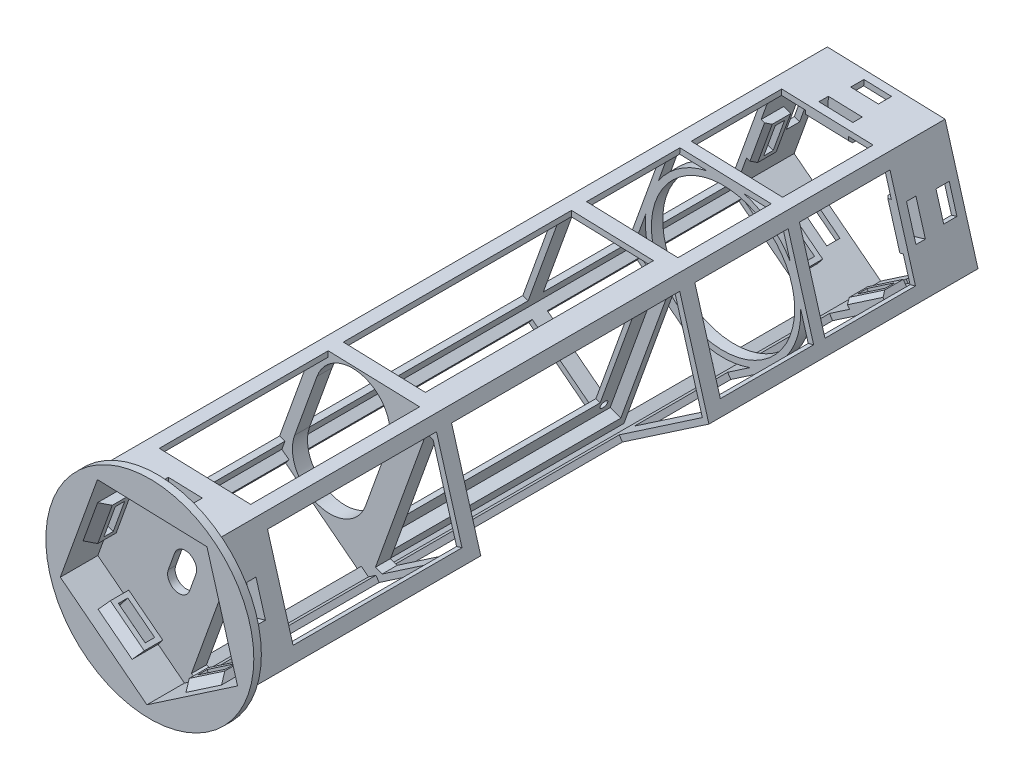
SolidWorks part; units mm, degrees
note: '?' marks a value the reader was unsure of.
ref_plane "Front Plane" through (0, 0, 0) normal (0, 0, 1) x (1, 0, 0)
ref_plane "Top Plane" through (0, 0, 0) normal (0, 1, 0) x (1, 0, 0)
ref_plane "Right Plane" through (0, 0, 0) normal (1, 0, 0) x (0, 0, -1)
sketch "Sketch3" plane through (0, 0, 0) normal (0, 0, 1) x (1, 0, 0)
  line L0 (0, 0) -> (16.2851, 21.0012) construction
  line L1 (15.1489, 19.536) -> (-13.8986, 20.4445)
  line L2 (-13.8986, 20.4445) -> (-23.7387, -6.9006)
  line L3 (-23.7387, -6.9006) -> (-0.7728, -24.7093)
  line L4 (-0.7728, -24.7093) -> (23.2611, -8.3705)
  line L5 (0, 0) -> (29.9163, 0) construction
  line L6 (0, 0) -> (25.0057, -8.9983) construction
  line L10 (-0.8307, -26.5625) -> (25.0057, -8.9983)
  line L11 (25.0057, -8.9983) -> (16.2851, 21.0012)
  line L12 (16.2851, 21.0012) -> (-14.941, 21.9778)
  line L13 (-14.941, 21.9778) -> (-25.5191, -7.4182)
  line L14 (-25.5191, -7.4182) -> (-0.8307, -26.5625)
  line L15 (23.2611, -8.3705) -> (15.1489, 19.536)
  circle A0 centre (0, 0) radius 20 construction
  dimension "D2" = 40
extrude "Boss-Extrude2" add sketch "Sketch3" along normal blind 190
ref_plane "Plane1" through (0, 0, 95) normal (0, 0, 1) x (1, 0, 0)
sketch "Sketch4" plane through (-20.23, 7.2798, 21.5) normal (0.9409, -0.3386, 0) x (-0.1146, -0.3186, -0.9409)
  line L8 (-154.443, -68.4581) -> (24.334, -4.1249)
  line L9 (-144.0928, -64.7335) -> (13.9838, -7.8495)
  line L11 (-162.6511, -45.6486) -> (16.126, 18.6845)
  line L12 (-152.3008, -41.9241) -> (5.7758, 14.96)
  line L14 (4.5907, 18.2532) -> (15.1689, -11.1427)
  line L15 (5.7758, 14.96) -> (13.9838, -7.8495)
  line L17 (-153.4859, -38.6308) -> (-142.9077, -68.0268)
  line L18 (-152.3008, -41.9241) -> (-144.0928, -64.7335)
  dimension "D1" = 3.5
  dimension "D2" = 3.5
  dimension "D3" = 11
  dimension "D4" = 11
extrude "Cut-Extrude1" cut sketch "Sketch4" along normal up to next
ref_point "Point1"
ref_axis "Axis1" through (0, 0, 190) along (0, 0, 1)?
pattern_circular "CirPattern1" count 5 over 360 about axis through (0, 0, 0) along (0, 0, 1) of "Cut-Extrude1"
ref_plane "Plane2" through (0, 0, 95) normal (0, 0, 1) x (1, 0, 0)
sketch "Sketch5" plane through (0, 0, 95) normal (0, 0, 1) x (1, 0, 0)
  line L0 (-2.0696, -25.6018) -> (14.7182, 21.0502) construction
  line L2 (-24.1133, -8.5083) -> (-1.8275, -25.7895) construction
  line L3 (23.2611, -8.3705) -> (0, 0) construction
  line L4 (-5.5594, -22.8957) -> (10.3043, 21.1882)
  line L8 (-2.0696, -25.6018) -> (-5.5594, -22.8957)
  line L10 (14.7182, 21.0502) -> (10.3043, 21.1882)
  line L11 (-2.0696, -25.6018) -> (14.7182, 21.0502)
  line L12 (-22.8004, 22.2236) -> (6.2471, 21.3151) construction
  dimension "D1" = 18
  dimension "D2" = 4.2
extrude "Boss-Extrude3" add sketch "Sketch5" along normal mid plane 64.5
sketch "Sketch6" plane through (0, 0, 127.25) normal (0, 0, 1) x (1, 0, 0)
  line L5 (-25.5191, -7.4182) -> (-0.8307, -26.5625)
  line L6 (-0.8307, -26.5625) -> (25.0057, -8.9983)
  line L7 (25.0057, -8.9983) -> (16.2851, 21.0012)
  line L8 (16.2851, 21.0012) -> (-14.941, 21.9778)
  line L9 (-14.941, 21.9778) -> (-25.5191, -7.4182)
  line L10 (-25.5191, -7.4182) -> (-0.8307, -26.5625)
  line L11 (-0.8307, -26.5625) -> (25.0057, -8.9983)
  line L12 (25.0057, -8.9983) -> (16.2851, 21.0012)
  line L13 (16.2851, 21.0012) -> (-14.941, 21.9778)
  line L14 (-14.941, 21.9778) -> (-25.5191, -7.4182)
  dimension "D1" = 0
extrude "Boss-Extrude4" add sketch "Sketch6" along normal blind 4
sketch "Sketch8" plane through (6.3243, -2.2758, 0) normal (0.9409, -0.3386, 0) x (0, 0, -1)
  line L0 (-62.75, 0) -> (-127.25, 0) construction
  line L1 (-127.25, -23.2131) -> (-127.25, 23.2131) construction
  line L3 (-62.75, -23.2131) -> (-62.75, 23.2131) construction
  line L5 (-125.5, -20.5) -> (-125.5, 20.5)
  line L6 (-125.5, -20.5) -> (-64.5, -20.5)
  line L7 (-125.5, 20.5) -> (-64.5, 20.5)
  line L8 (-64.5, -20.5) -> (-64.5, 20.5)
  line L14 (-64.5, 20.5) -> (-125.5, -20.5) construction
  line L15 (-64.5, -20.5) -> (-125.5, 20.5) construction
  point P11 (-95, 0)
  point P14 (-95, 0)
  dimension "D1" = 61
  dimension "D2" = 41
extrude "Cut-Extrude3" cut sketch "Sketch8" against normal blind 3
sketch "Sketch9" plane through (3.5015, -1.26, 0) normal (0.9409, -0.3386, 0) x (0, 0, -1)
  line L8 (-121.5, -16.5) -> (-68.5, -16.5)
  line L9 (-68.5, -16.5) -> (-68.5, 16.5)
  line L10 (-68.5, 16.5) -> (-121.5, 16.5)
  line L11 (-121.5, 16.5) -> (-121.5, -16.5)
  line L12 (-121.5, -16.5) -> (-68.5, -16.5)
  line L13 (-68.5, -16.5) -> (-68.5, 16.5)
  line L14 (-68.5, 16.5) -> (-121.5, 16.5)
  line L15 (-121.5, 16.5) -> (-121.5, -16.5)
  dimension "D1" = 4
extrude "Cut-Extrude4" cut sketch "Sketch9" against normal up to surface (1.2 mm away) up to face at (2.3724, -0.8537, 95)
sketch "Sketch10" plane through (0, 0, 62.75) normal (0, 0, -1) x (-1, 0, 0)
  line L25 (-23.2611, -8.3705) -> (0.7728, -24.7093)
  line L26 (0.7728, -24.7093) -> (23.7387, -6.9006)
  line L27 (23.7387, -6.9006) -> (13.8986, 20.4445)
  line L28 (13.8986, 20.4445) -> (-15.1489, 19.536)
  line L29 (-15.1489, 19.536) -> (-23.2611, -8.3705)
  line L30 (0.8307, -26.5625) -> (25.5191, -7.4182)
  line L31 (-25.0057, -8.9983) -> (0.8307, -26.5625)
  line L32 (-16.2851, 21.0012) -> (-25.0057, -8.9983)
  line L33 (14.941, 21.9778) -> (-16.2851, 21.0012)
  line L34 (25.5191, -7.4182) -> (14.941, 21.9778)
  line L40 (0.8307, -26.5625) -> (25.5191, -7.4182)
  line L41 (-25.0057, -8.9983) -> (0.8307, -26.5625)
  line L42 (-16.2851, 21.0012) -> (-25.0057, -8.9983)
  line L43 (14.941, 21.9778) -> (-16.2851, 21.0012)
  line L44 (25.5191, -7.4182) -> (14.941, 21.9778)
  dimension "D1" = 0
extrude "Boss-Extrude5" add sketch "Sketch10" against normal blind 4
sketch "Sketch11" plane through (0, 0, 62.75) normal (0, 0, -1) x (-1, 0, 0)
  line L0 (5.0254, -21.4117) -> (5.5594, -22.8957)
  line L1 (5.5594, -22.8957) -> (3.6676, -24.3627)
  line L2 (-9.7702, 19.7042) -> (-10.3043, 21.1882)
  line L3 (-10.3043, 21.1882) -> (-12.697, 21.1134)
  line L4 (21.8341, -8.3776) -> (5.0254, -21.4117)
  line L7 (5.0254, -21.4117) -> (-9.7702, 19.7042)
  line L9 (-14.1842, 19.5662) -> (1.5355, -24.1178)
  line L10 (-14.1842, 19.5662) -> (1.5355, -24.1178)
  line L11 (-12.7868, 21.1106) -> (11.4427, 21.8684) construction
  line L13 (5.0254, -21.4117) -> (-10.0783, 20.5603) construction
  line L18 (22.7533, -9.5629) -> (3.5966, -24.4177) construction
  line L19 (5.0254, -21.4117) -> (-9.7702, 19.7042)
  line L27 (-9.7702, 19.7042) -> (11.4896, 20.3691)
  line L49 (3.5966, -24.4177) -> (22.7533, -9.5629)
  line L51 (11.4427, 21.8684) -> (-12.7868, 21.1106)
  line L52 (22.7533, -9.5629) -> (21.8341, -8.3776)
  line L53 (22.7533, -9.5629) -> (21.8341, -8.3776)
  line L54 (11.4896, 20.3691) -> (11.4427, 21.8684)
  line L55 (11.4896, 20.3691) -> (11.4427, 21.8684)
  line L56 (-12.7868, 21.1106) -> (-12.7399, 19.6113)
  line L57 (-12.7868, 21.1106) -> (-12.7399, 19.6113)
  line L58 (-12.7399, 19.6113) -> (-14.1842, 19.5662)
  line L59 (-12.7399, 19.6113) -> (-14.1842, 19.5662)
  line L60 (1.5355, -24.1178) -> (2.6774, -23.2323)
  line L61 (1.5355, -24.1178) -> (2.6774, -23.2323)
  line L62 (2.6774, -23.2323) -> (3.5966, -24.4177)
  line L63 (2.6774, -23.2323) -> (3.5966, -24.4177)
  dimension "D1" = 0
ref_plane "Plane3" through (0, 0, 35) normal (0, 0, 1) x (1, 0, 0)
sketch "Sketch14" plane through (0, 0, 35) normal (0, 0, 1) x (1, 0, 0)
  line L5 (-25.5191, -7.4182) -> (-0.8307, -26.5625)
  line L6 (-0.8307, -26.5625) -> (25.0057, -8.9983)
  line L7 (25.0057, -8.9983) -> (16.2851, 21.0012)
  line L8 (16.2851, 21.0012) -> (-14.941, 21.9778)
  line L9 (-14.941, 21.9778) -> (-25.5191, -7.4182)
  line L11 (-0.8307, -26.5625) -> (25.0057, -8.9983)
  line L12 (25.0057, -8.9983) -> (16.2851, 21.0012)
  line L16 (23.2611, -8.3705) -> (15.3259, -13.7651)
  line L18 (-0.7728, -24.7093) -> (-8.3554, -18.8294)
  line L20 (-23.7387, -6.9006) -> (-20.4898, 2.1279)
  line L22 (-13.8986, 20.4445) -> (-4.308, 20.1445)
  line L24 (15.1489, 19.536) -> (17.8273, 10.3221)
  line L25 (7.1625, -19.3147) -> (-0.7728, -24.7093)
  line L26 (20.5827, 0.8433) -> (23.2611, -8.3705)
  line L27 (5.5584, 19.8359) -> (15.1489, 19.536)
  line L28 (-17.1475, 11.416) -> (-13.8986, 20.4445)
  line L29 (-16.1561, -12.7805) -> (-23.7387, -6.9006)
  line L30 (16.2851, 21.0012) -> (-14.941, 21.9778)
  line L31 (-14.941, 21.9778) -> (-25.5191, -7.4182)
  line L32 (-25.5191, -7.4182) -> (-0.8307, -26.5625)
  circle A3 centre (0, 0) radius 19
  arc A8 (15.3259, -13.7651) -> (20.5827, 0.8433) centre (0, 0) ccw
  circle A9 centre (0, 0) radius 20.6 construction
  arc A10 (17.8273, 10.3221) -> (5.5584, 19.8359) centre (0, 0) ccw
  arc A11 (-4.308, 20.1445) -> (-17.1475, 11.416) centre (0, 0) ccw
  arc A12 (-20.4898, 2.1279) -> (-16.1561, -12.7805) centre (0, 0) ccw
  arc A13 (-8.3554, -18.8294) -> (7.1625, -19.3147) centre (0, 0) ccw
  dimension "D2" = 38
  dimension "D1" = 0
  dimension "D3" = 1.6
extrude "Boss-Extrude8" add sketch "Sketch14" along normal blind 3
ref_plane "Plane4" through (0, 0, 32) normal (0, 0, -1) x (-1, 0, 0)
sketch "Sketch15" plane through (0, 0, 32) normal (0, 0, -1) x (-1, 0, 0)
  line L0 (-23.2611, -8.3705) -> (0.7728, -24.7093)
  line L1 (0.7728, -24.7093) -> (23.7387, -6.9006)
  line L2 (23.7387, -6.9006) -> (13.8986, 20.4445)
  line L3 (13.8986, 20.4445) -> (-15.1489, 19.536)
  line L4 (-15.1489, 19.536) -> (-23.2611, -8.3705)
  line L5 (0.8307, -26.5625) -> (25.5191, -7.4182)
  line L6 (-25.0057, -8.9983) -> (0.8307, -26.5625)
  line L7 (-16.2851, 21.0012) -> (-25.0057, -8.9983)
  line L8 (14.941, 21.9778) -> (-16.2851, 21.0012)
  line L9 (25.5191, -7.4182) -> (14.941, 21.9778)
  line L10 (0.8307, -26.5625) -> (25.5191, -7.4182)
  line L11 (-25.0057, -8.9983) -> (0.8307, -26.5625)
  line L12 (-16.2851, 21.0012) -> (-25.0057, -8.9983)
  line L13 (14.941, 21.9778) -> (-16.2851, 21.0012)
  line L14 (25.5191, -7.4182) -> (14.941, 21.9778)
  dimension "D1" = 0
sketch "Sketch29" plane through (0, 0, 190) normal (0, 0, 1) x (1, 0, 0)
  line L5 (-25.5191, -7.4182) -> (-0.8307, -26.5625)
  line L6 (-0.8307, -26.5625) -> (25.0057, -8.9983)
  line L7 (25.0057, -8.9983) -> (16.2851, 21.0012)
  line L8 (16.2851, 21.0012) -> (-14.941, 21.9778)
  line L9 (-14.941, 21.9778) -> (-25.5191, -7.4182)
  line L10 (-25.5191, -7.4182) -> (-0.8307, -26.5625)
  line L11 (-0.8307, -26.5625) -> (25.0057, -8.9983)
  line L12 (25.0057, -8.9983) -> (16.2851, 21.0012)
  line L13 (16.2851, 21.0012) -> (-14.941, 21.9778)
  line L14 (-14.941, 21.9778) -> (-25.5191, -7.4182)
  dimension "D1" = 0
sketch "Sketch31" [suppressed] plane through (0, 0, 186.4) normal (0, 0, 1) x (1, 0, 0)
  line L0 (25.0057, -8.9983) -> (0, 0) construction
  line L1 (12.0432, 0.9801) -> (8.6573, -8.4292)
  line L2 (12.0432, 0.9801) -> (-8.6573, 8.4292)
  line L3 (8.6573, -8.4292) -> (-12.0432, -0.9801)
  line L4 (-8.6573, 8.4292) -> (-12.0432, -0.9801)
  line L5 (12.0432, 0.9801) -> (-12.0432, -0.9801) construction
  line L6 (8.6573, -8.4292) -> (-8.6573, 8.4292) construction
  line L7 (-10.3503, 3.7246) -> (10.3503, -3.7246) construction
  dimension "D1" = 22
  dimension "D2" = 10
extrude "Cut-Extrude9" [suppressed] cut sketch "Sketch31" against normal up to surface (1.4 mm away)
sketch "Sketch32" [suppressed] plane through (0, 0, 187) normal (0, 0, 1) x (1, 0, 0)
  line L0 (0, 0) -> (-36.3954, 13.0969) construction
  line L1 (-22.7695, 0.2228) -> (-21.2398, -0.3276)
  line L3 (-14.941, 21.9778) -> (-25.5191, -7.4182) construction
  line L4 (-17.6906, 14.3368) -> (-16.1609, 13.7863)
  line L5 (-18.5086, 9.8487) -> (-20.5401, 4.2031) construction
  line L6 (-18.5086, 9.8487) -> (-20.5401, 4.2031)
  line L7 (-17.6906, 14.3368) -> (-22.7695, 0.2228)
  arc A0 (-20.5401, 4.2031) -> (-13.3121, -11.1513) centre (-9.2489, 0.1399) ccw construction
  arc A1 (-20.5401, 4.2031) -> (-13.3121, -11.1513) centre (-9.2489, 0.1399) ccw construction
  arc A3 (-3.1542, 17.0767) -> (-18.5086, 9.8487) centre (-7.2174, 5.7855) ccw construction
  arc A4 (-16.1609, 13.7863) -> (-18.5086, 9.8487) centre (-7.2174, 5.7855) ccw
  arc A5 (-20.5401, 4.2031) -> (-21.2398, -0.3276) centre (-9.2489, 0.1399) ccw
  dimension "D1" = 7.5
sketch "Sketch34" [suppressed] plane through (0, 0, 186.4) normal (0, 0, 1) x (1, 0, 0)
  line L0 (-22.7695, 0.2228) -> (-17.6906, 14.3368)
  line L1 (-22.7695, 0.2228) -> (-22.0638, -0.0311)
  line L2 (-17.6906, 14.3368) -> (-16.9849, 14.0828)
  line L3 (-22.0638, -0.0311) -> (-16.9849, 14.0828)
  line L4 (-13.3121, -11.1513) -> (3.1542, -17.0767)
  line L5 (18.5086, -9.8487) -> (20.5401, -4.2031)
  line L6 (13.3121, 11.1513) -> (-3.1542, 17.0767)
  line L7 (-18.5086, 9.8487) -> (-20.5401, 4.2031)
  line L8 (-13.3121, -11.1513) -> (3.1542, -17.0767) construction
  line L9 (18.5086, -9.8487) -> (20.5401, -4.2031) construction
  line L10 (13.3121, 11.1513) -> (-3.1542, 17.0767) construction
  line L11 (-18.5086, 9.8487) -> (-20.5401, 4.2031) construction
  arc A4 (3.1542, -17.0767) -> (18.5086, -9.8487) centre (7.2174, -5.7855) ccw
  arc A5 (20.5401, -4.2031) -> (13.3121, 11.1513) centre (9.2489, -0.1399) ccw
  arc A6 (-3.1542, 17.0767) -> (-18.5086, 9.8487) centre (-7.2174, 5.7855) ccw
  arc A7 (-20.5401, 4.2031) -> (-13.3121, -11.1513) centre (-9.2489, 0.1399) ccw
  arc A8 (3.1542, -17.0767) -> (18.5086, -9.8487) centre (7.2174, -5.7855) ccw construction
  arc A9 (20.5401, -4.2031) -> (13.3121, 11.1513) centre (9.2489, -0.1399) ccw construction
  arc A10 (-3.1542, 17.0767) -> (-18.5086, 9.8487) centre (-7.2174, 5.7855) ccw construction
  arc A11 (-20.5401, 4.2031) -> (-13.3121, -11.1513) centre (-9.2489, 0.1399) ccw construction
  dimension "D1" = 0
sketch "Sketch61" plane through (3.5015, -1.26, 0) normal (0.9409, -0.3386, 0) x (0, 0, -1)
  line L0 (-125.5, 20.5) -> (-125.5, -20.5) construction
  line L1 (-125.5, -20.5) -> (-64.5, -20.5) construction
  line L2 (-64.5, 0) -> (-125.5, 0) construction
  line L3 (-64.5, -20.5) -> (-64.5, 20.5) construction
  line L4 (-95, 20.5) -> (-95, -20.5) construction
  line L5 (-64.5, 20.5) -> (-125.5, 20.5) construction
  line L6 (-125.5, -20.5) -> (-64.5, -20.5) construction
  circle A0 centre (-123, -18) radius 1
  circle A1 centre (-67, -18) radius 1
  circle A2 centre (-123, 18.5) radius 1
  circle A3 centre (-67, 18.5) radius 1
  point P22 (0, 0)
  point P23 (0, 0)
  point P24 (0, 0)
  point P25 (0, 0)
  dimension "D3" = 2
  dimension "D1" = 2.5
  dimension "D2" = 2.5
  dimension "D4" = 2
  dimension "D5" = 2.5
extrude "Cut-Extrude22" cut sketch "Sketch61" against normal up to surface (1.2 mm away) up to face at (2.3724, -0.8537, 95)
sketch "Sketch62" plane through (0, 0, 190) normal (0, 0, 1) x (1, 0, 0)
  line L0 (23.2611, -8.3705) -> (15.1489, 19.536) construction
  line L1 (23.2611, -8.3705) -> (15.1489, 19.536)
  line L2 (15.1489, 19.536) -> (-13.8986, 20.4445) construction
  line L3 (-13.8986, 20.4445) -> (-23.7387, -6.9006) construction
  line L4 (-23.7387, -6.9006) -> (-0.7728, -24.7093) construction
  line L5 (-0.7728, -24.7093) -> (23.2611, -8.3705) construction
  line L6 (15.1489, 19.536) -> (-13.8986, 20.4445)
  line L7 (-13.8986, 20.4445) -> (-23.7387, -6.9006)
  line L8 (-23.7387, -6.9006) -> (-0.7728, -24.7093)
  line L9 (-0.7728, -24.7093) -> (23.2611, -8.3705)
  circle A0 centre (0, 0) radius 26.5755 construction
  circle A1 centre (0, 0) radius 27.5755
  dimension "D1" = 1
extrude "Boss-Extrude16" add sketch "Sketch62" against normal blind 2
sketch "Sketch64" plane through (-20.23, 7.2798, 0) normal (-0.9409, 0.3386, 0) x (0, 0, 1)
  line L0 (179, 12.1207) -> (179, -12.1207) construction
  line L1 (181.25, -4.5) -> (183.75, -4.5)
  line L2 (181.25, -4.5) -> (181.25, 4.5)
  line L3 (181.25, 4.5) -> (183.75, 4.5)
  line L4 (183.75, -4.5) -> (183.75, 4.5)
  line L5 (181.25, -4.5) -> (183.75, 4.5) construction
  line L6 (181.25, 4.5) -> (183.75, -4.5) construction
  line L7 (6.25, -4.5) -> (8.75, -4.5)
  line L8 (6.25, -4.5) -> (6.25, 4.5)
  line L9 (6.25, 4.5) -> (8.75, 4.5)
  line L10 (8.75, -4.5) -> (8.75, 4.5)
  line L11 (0, 15.6207) -> (0, -15.6207) construction
  line L12 (11, -12.1207) -> (11, 12.1207) construction
  point P0 (182.5, 0)
  point P7 (179, 0)
  point P14 (0, 0)
  point P15 (6.25, 0)
  dimension "D1" = 2.5
  dimension "D2" = 9
  dimension "D3" = 2.25
  dimension "D4" = 2.25
extrude "Cut-Extrude23" cut sketch "Sketch64" against normal up to next
sketch "Sketch68" plane through (-18.8186, 6.7719, 0) normal (0.9409, -0.3386, 0) x (0, 0, -1)
  line L0 (-181.25, -4.5) -> (-183.75, -4.5) construction
  line L1 (-183.75, -4.5) -> (-183.75, 4.5) construction
  line L2 (-183.75, 4.5) -> (-181.25, 4.5) construction
  line L3 (-181.25, 4.5) -> (-181.25, -4.5) construction
  line L4 (-181.25, -4.5) -> (-183.75, -4.5)
  line L5 (-183.75, -4.5) -> (-183.75, 4.5)
  line L6 (-183.75, 4.5) -> (-181.25, 4.5)
  line L7 (-181.25, 4.5) -> (-181.25, -4.5)
  line L8 (-180.05, -5.7) -> (-184.95, -5.7)
  line L9 (-184.95, -5.7) -> (-184.95, 5.7)
  line L10 (-184.95, 5.7) -> (-180.05, 5.7)
  line L11 (-180.05, 5.7) -> (-180.05, -5.7)
  line L12 (-8.75, 4.5) -> (-6.25, 4.5) construction
  line L13 (-8.75, -4.5) -> (-8.75, 4.5) construction
  line L14 (-6.25, -4.5) -> (-8.75, -4.5) construction
  line L15 (-6.25, 4.5) -> (-6.25, -4.5) construction
  line L16 (-8.75, 4.5) -> (-6.25, 4.5)
  line L17 (-8.75, -4.5) -> (-8.75, 4.5)
  line L18 (-6.25, -4.5) -> (-8.75, -4.5)
  line L19 (-6.25, 4.5) -> (-6.25, -4.5)
  line L20 (-9.95, 5.7) -> (-5.05, 5.7)
  line L21 (-5.05, 5.7) -> (-5.05, -5.7)
  line L22 (-5.05, -5.7) -> (-9.95, -5.7)
  line L23 (-9.95, -5.7) -> (-9.95, 5.7)
  dimension "D1" = 1.2
  dimension "D2" = 1.2
extrude "Boss-Extrude19" add sketch "Sketch68" along normal blind 2
pattern_circular "CirPattern2" count 5 over 360 about axis through (0, 0, 0) along (0, 0, 1) of "Cut-Extrude23", "Boss-Extrude19"
chamfer "Chamfer1" distance 2 angle 45 30 edges at (-18.8186, 6.7719, 184.95) (-15.9477, 11.7966, 184.95) (-19.8077, 1.07, 184.95) (-18.8186, 6.7719, 9.95) (-15.9477, 11.7966, 9.95) (-19.8077, 1.07, 9.95) (0.6252, 19.9902, 184.95) (6.2911, 18.8125, 184.95) (-5.1033, 19.1689, 184.95) (0.6252, 19.9902, 9.95) (6.2911, 18.8125, 9.95) (-5.1033, 19.1689, 9.95) (19.205, 5.5827, 184.95) (19.8359, -0.1698, 184.95) (16.6537, 10.777, 184.95) (19.205, 5.5827, 9.95) (19.8359, -0.1698, 9.95) (16.6537, 10.777, 9.95) (11.2442, -16.5399, 184.95) (5.9681, -18.9175, 184.95) (15.3958, -12.5083, 184.95) (11.2442, -16.5399, 9.95) (5.9681, -18.9175, 9.95) (15.3958, -12.5083, 9.95) (-12.2557, -15.805, 184.95) (-16.1474, -11.5218, 184.95) (-7.1385, -18.5076, 184.95) (-12.2557, -15.805, 9.95) (-16.1474, -11.5218, 9.95) (-7.1385, -18.5076, 9.95)
sketch "Sketch38" plane through (0, 0, 127.25) normal (0, 0, -1) x (-1, 0, 0)
  line L5 (-22.5883, -6.0562) -> (-15.8217, 17.2216) construction
  line L6 (-1.2204, -23.3543) -> (-21.2679, -9.7256) construction
  line L11 (-16.3738, 15.3225) -> (-23.2611, -8.3705)
  line L12 (-23.2611, -8.3705) -> (-2.856, -22.2424)
  line L16 (-1.071, -21.6) -> (-2.856, -22.2424)
  line L17 (0.03, -24.6596) -> (-15.6897, 19.0244)
  line L18 (-1.071, -21.6) -> (-14.5887, 15.9649)
  line L19 (-14.5887, 15.9649) -> (-16.3738, 15.3225)
  dimension "D3" = 1.6
  dimension "D1" = 1.6
  dimension "D2" = 1.6
extrude "Cut-Extrude14" cut sketch "Sketch38" against normal up to surface (4 mm away) up to face at (0, 0, 131.25)
ref_plane "Plane5" through (14.5887, 15.9649, 127.25) normal (0.3386, 0.9409, 0) x (0.9409, -0.3386, 0)
sketch "Sketch42" plane through (0, 0, 131.25) normal (0, 0, 1) x (1, 0, 0)
  line L0 (-20.23, 7.2798) -> (0, 0) construction
  line L1 (-16.126, 18.6845) -> (-24.334, -4.1249) construction
  line L2 (5.4365, -16.774) -> (-14.8782, -9.4637) construction
  line L3 (5.4365, -16.774) -> (14.8782, 9.4637) construction
  line L4 (-14.8782, -9.4637) -> (-5.4365, 16.774) construction
  line L5 (14.8782, 9.4637) -> (-5.4365, 16.774) construction
  line L6 (5.4365, -16.774) -> (-5.4365, 16.774) construction
  line L7 (-14.8782, -9.4637) -> (14.8782, 9.4637) construction
  line L8 (-3.9066, 13.524) -> (11.6282, 7.9338) construction
  line L9 (4.7208, 13.1189) -> (-4.7208, -13.1189) construction
  line L10 (2.2472, -13.2032) -> (-10.1449, -8.7439) construction
  line L11 (-1.5355, -24.1178) -> (14.1842, 19.5662) construction
  line L12 (-1.5355, -24.1178) -> (14.1842, 19.5662)
  line L13 (12.891, 3.9416) -> (6.1392, -14.8212) construction
  line L14 (12.891, 3.9416) -> (10.6328, 4.7542) construction
  line L15 (6.1392, -14.8212) -> (3.881, -14.0086) construction
  line L16 (10.6328, 4.7542) -> (3.881, -14.0086) construction
  circle A0 centre (11.6282, 7.9338) radius 1
  circle A1 centre (-3.9066, 13.524) radius 1
  circle A2 centre (2.2472, -13.2032) radius 1
  circle A3 centre (-10.1449, -8.7439) radius 1
  point P1 (3.8608, 10.7289)
  point P2 (0, 0)
  point P19 (-3.9488, -10.9735)
  dimension "D4" = 2
  dimension "D7" = 2
  dimension "D1" = 21.59
  dimension "D2" = 27.8848
  dimension "D3" = 16.51
  dimension "D5" = 2.54
  dimension "D6" = 13.17
  dimension "D8" = 2.28
  dimension "D9" = 2.4
sketch "Sketch43" plane through (0, 0, 131.25) normal (0, 0, 1) x (1, 0, 0)
  line L1 (10.8306, 5.5214) -> (12.5507, 10.3013)
  line L2 (12.891, 3.9416) -> (10.6328, 4.7542) construction
  line L3 (12.891, 3.9416) -> (10.6328, 4.7542)
  line L4 (1.071, -21.6) -> (14.5887, 15.9649) construction
  arc A0 (12.5507, 10.3013) -> (10.8306, 5.5214) centre (11.6282, 7.9338) cw
  point P4 (12.5507, 10.3013)
  line M27 (1.071, -21.6) -> (14.5887, 15.9649)
  dimension "D1" = 2.5409
extrude "Boss-Extrude15" [suppressed] add sketch "Sketch43" against normal up to surface (4 mm away) contours A0 M27
sketch "Sketch44" plane through (0, 0, 131.25) normal (0, 0, 1) x (1, 0, 0)
  circle A0 centre (-10.1449, -8.7439) radius 1 construction
  circle A1 centre (-3.9066, 13.524) radius 1 construction
  circle A2 centre (-10.1449, -8.7439) radius 1
  circle A3 centre (-3.9066, 13.524) radius 1
extrude "Cut-Extrude18" [suppressed] cut sketch "Sketch42" against normal blind 3.5 contours A0 | A2
extrude "Cut-Extrude19" [suppressed] cut sketch "Sketch44" against normal blind 1.5
sketch "Sketch45" plane through (0, 0, 131.25) normal (0, 0, 1) x (1, 0, 0)
  line L0 (-3.2144, -16.3791) -> (7.9593, 14.6717) construction
  line L1 (-3.2144, -16.3791) -> (9.3136, 18.4354) construction
  line L2 (13.2655, 17.0133) -> (-0.6169, -21.5649) construction
  line L3 (13.2655, 17.0133) -> (-0.6169, -21.5649) construction
  line L4 (-5.5594, -22.8957) -> (10.3043, 21.1882)
  line L5 (10.3043, 21.1882) -> (14.7182, 21.0502)
  line L6 (14.7182, 21.0502) -> (-2.0696, -25.6018)
  line L7 (-2.0696, -25.6018) -> (-5.5594, -22.8957)
  line L8 (-22.7533, -9.5629) -> (-3.5966, -24.4177) construction
  line L11 (12.7868, 21.1106) -> (-11.4427, 21.8684) construction
sketch "Sketch46" plane through (0, 0, 131.25) normal (0, 0, 1) x (1, 0, 0)
  line L0 (-8.1098, 21.7641) -> (-20.1403, -11.5891)
  line L1 (-8.1098, 21.7641) -> (-4.6098, 21.6547)
  line L2 (-20.1403, -11.5891) -> (-17.3745, -13.7339)
  line L3 (-4.6098, 21.6547) -> (-17.3745, -13.7339)
  line L4 (-16.126, 18.6845) -> (-24.334, -4.1249) construction
  line L5 (-1.5355, -24.1178) -> (14.1842, 19.5662) construction
  line L6 (-1.5355, -24.1178) -> (14.1842, 19.5662)
  line L8 (12.7868, 21.1106) -> (-11.4427, 21.8684) construction
  line L9 (-22.7533, -9.5629) -> (-3.5966, -24.4177) construction
  dimension "D1" = 3.5
  dimension "D2" = 3.5
  dimension "D3" = 6.5
sketch "Sketch65" plane through (0, 0, 0) normal (0, 0, -1) x (-1, 0, 0)
  line L0 (23.7387, -6.9006) -> (0.7728, -24.7093) construction
  line L1 (13.8986, 20.4445) -> (23.7387, -6.9006) construction
  line L2 (-15.1489, 19.536) -> (13.8986, 20.4445) construction
  line L3 (-23.2611, -8.3705) -> (-15.1489, 19.536) construction
  line L4 (0.7728, -24.7093) -> (-23.2611, -8.3705) construction
  line L5 (0.8307, -26.5625) -> (25.5191, -7.4182)
  line L6 (25.5191, -7.4182) -> (14.941, 21.9778)
  line L7 (14.941, 21.9778) -> (-16.2851, 21.0012)
  line L8 (-16.2851, 21.0012) -> (-25.0057, -8.9983)
  line L9 (-25.0057, -8.9983) -> (0.8307, -26.5625)
  line L10 (0.8307, -26.5625) -> (25.5191, -7.4182)
  line L11 (25.5191, -7.4182) -> (14.941, 21.9778)
  line L12 (14.941, 21.9778) -> (-16.2851, 21.0012)
  line L13 (-16.2851, 21.0012) -> (-25.0057, -8.9983)
  line L14 (-25.0057, -8.9983) -> (0.8307, -26.5625)
  line L15 (23.7387, -6.9006) -> (0.7728, -24.7093)
  line L16 (13.8986, 20.4445) -> (23.7387, -6.9006)
  line L17 (-15.1489, 19.536) -> (13.8986, 20.4445)
  line L18 (-23.2611, -8.3705) -> (-15.1489, 19.536)
  line L19 (0.7728, -24.7093) -> (-23.2611, -8.3705)
  dimension "D1" = 0
extrude "Boss-Extrude17" add sketch "Sketch65" along normal blind 4.6
sketch "Sketch66" plane through (0, 0, -4.6) normal (0, 0, -1) x (-1, 0, 0)
  line L0 (-15.3259, -13.7651) -> (-20.5827, 0.8433) construction
  line L1 (-16.0294, -13.2868) -> (-20.8202, 0.0265)
  line L2 (-23.2611, -8.3705) -> (0.7728, -24.7093) construction
  line L3 (-15.1489, 19.536) -> (-23.2611, -8.3705) construction
  line L4 (-20.8202, 0.0265) -> (-21.58, -2.5874)
  line L5 (-21.58, -2.5874) -> (-18.2805, -11.7565)
  line L6 (-18.2805, -11.7565) -> (-16.0294, -13.2868)
  dimension "D1" = 0.5
  dimension "D2" = 1.6
extrude "Boss-Extrude18" add sketch "Sketch66" against normal offset from surface (8.85 mm away) 2 up to face at (18.965, 5.5129, 6.25)
sketch "Sketch67" plane through (18.4248, -6.6302, 0) normal (-0.9409, 0.3386, 0) x (0, 0, 1)
  line L0 (-4.6, -7.0745) -> (-4.6, 7.0745) construction
  line L1 (1.15, -3.6723) -> (-2.35, -3.6723)
  line L2 (1.15, -3.6723) -> (1.15, 3.6723)
  line L3 (1.15, 3.6723) -> (-2.35, 3.6723)
  line L4 (-2.35, -3.6723) -> (-2.35, 3.6723)
  line L5 (1.15, -3.6723) -> (-2.35, 3.6723) construction
  line L6 (1.15, 3.6723) -> (-2.35, -3.6723) construction
  point P0 (-0.6, 0)
  dimension "D1" = 3.5
  dimension "D2" = 2.25
  dimension "D3" = 1.2
  dimension "D4" = 1.2
extrude "Cut-Extrude24" cut sketch "Sketch67" against normal up to next and the other way up to next
pattern_circular "CirPattern3" count 5 over 360 about axis through (0, 0, 0) along (0, 0, 1) of "Boss-Extrude18", "Cut-Extrude24"
sketch "Sketch71" plane through (0, 0, 180.05) normal (0, 0, -1) x (-1, 0, 0)
  line L5 (0.8307, -26.5625) -> (25.5191, -7.4182)
  line L6 (-25.0057, -8.9983) -> (0.8307, -26.5625)
  line L7 (-16.2851, 21.0012) -> (-25.0057, -8.9983)
  line L8 (14.941, 21.9778) -> (-16.2851, 21.0012)
  line L9 (25.5191, -7.4182) -> (14.941, 21.9778)
  line L10 (0.8307, -26.5625) -> (25.5191, -7.4182)
  line L11 (-25.0057, -8.9983) -> (0.8307, -26.5625)
  line L12 (-16.2851, 21.0012) -> (-25.0057, -8.9983)
  line L13 (14.941, 21.9778) -> (-16.2851, 21.0012)
  line L14 (25.5191, -7.4182) -> (14.941, 21.9778)
  dimension "D1" = 0
extrude "Boss-Extrude20" add sketch "Sketch71" along normal blind 4
sketch "Sketch69" plane through (0, 0, -4.6) normal (0, 0, -1) x (-1, 0, 0)
  line L0 (-15.1489, 19.536) -> (-23.2611, -8.3705) construction
  line L1 (-23.2611, -8.3705) -> (0.7728, -24.7093) construction
  line L2 (0.7728, -24.7093) -> (23.7387, -6.9006) construction
  line L3 (13.8986, 20.4445) -> (-15.1489, 19.536) construction
  line L4 (23.7387, -6.9006) -> (13.8986, 20.4445) construction
  line L5 (-15.1489, 19.536) -> (-23.2611, -8.3705)
  line L6 (-23.2611, -8.3705) -> (0.7728, -24.7093)
  line L7 (0.7728, -24.7093) -> (23.7387, -6.9006)
  line L8 (13.8986, 20.4445) -> (-15.1489, 19.536)
  line L9 (23.7387, -6.9006) -> (13.8986, 20.4445)
extrude "Cut-Extrude25" cut sketch "Sketch69" against normal up to next
sketch "Sketch7" plane through (0, 0, 176.05) normal (0, 0, -1) x (-1, 0, 0)
  line L0 (-2.3724, -0.8537) -> (20.23, 7.2798) construction
  line L1 (-9.7702, 19.7042) -> (5.0254, -21.4117) construction
  line L2 (16.126, 18.6845) -> (24.334, -4.1249) construction
  line L4 (20.3499, -1.9764) -> (14.4244, 14.4899)
  line L5 (1.5312, -8.7483) -> (-4.3942, 7.718)
  line L7 (20.3499, -1.9764) -> (-4.3942, 7.718) construction
  line L8 (1.5312, -8.7483) -> (14.4244, 14.4899) construction
  line L9 (10.9405, -5.3623) -> (5.0151, 11.104) construction
  line L11 (-9.7702, 19.7042) -> (5.0254, -21.4117) construction
  arc A0 (-4.3942, 7.718) -> (14.4244, 14.4899) centre (5.0151, 11.104) cw
  arc A1 (1.5312, -8.7483) -> (20.3499, -1.9764) centre (10.9405, -5.3623) ccw
  point P7 (7.9778, 2.8708)
  point P9 (14.3265, -14.7716)
  point P14 (1.6292, 20.5133)
  dimension "D1" = 37.5
  dimension "D2" = 20
  dimension "D3" = 1
extrude "Cut-Extrude2" cut sketch "Sketch7" against normal blind 2 and the other way up to next
sketch "Sketch49" plane through (0, 0, 178.05) normal (0, 0, -1) x (-1, 0, 0)
  line L0 (-1.4315, -0.5151) -> (17.3871, 6.2568) construction
  line L1 (-4.3942, 7.718) -> (1.5312, -8.7483) construction
  line L2 (20.3499, -1.9764) -> (14.4244, 14.4899) construction
  line L3 (0.5448, 2.853) -> (2.2378, -1.8517) construction
  line L4 (3.3676, 3.8688) -> (5.0606, -0.8359)
  line L5 (-2.278, 1.8372) -> (-0.585, -2.8675)
  arc A0 (3.3676, 3.8688) -> (-2.278, 1.8372) centre (0.5448, 2.853) ccw
  arc A1 (-0.585, -2.8675) -> (5.0606, -0.8359) centre (2.2378, -1.8517) ccw
  point P8 (1.3913, 0.5007)
  dimension "D1" = 6
  dimension "D2" = 5
extrude "Cut-Extrude26" cut sketch "Sketch49" against normal up to next
sketch "Sketch70" plane through (0, 0, 127.25) normal (0, 0, -1) x (-1, 0, 0)
  line L0 (-24.0287, -5.6375) -> (-22.5883, -6.0562)
  line L1 (-16.3738, 15.3225) -> (-22.5883, -6.0562) construction
  line L2 (-22.5883, -6.0562) -> (-24.0287, -5.6375) construction
  line L3 (-22.5883, -6.0562) -> (-21.2679, -9.7256)
  line L4 (-21.2679, -9.7256) -> (-22.1112, -10.9661)
  line L5 (-22.1112, -10.9661) -> (-25.0057, -8.9983)
  line L6 (-25.0057, -8.9983) -> (-24.0287, -5.6375)
extrude "Cut-Extrude27" cut sketch "Sketch70" along normal up to surface (60.5 mm away) up to face at (19.9252, 5.7921, 66.75)
sketch "Sketch72" plane through (0, 0, 176.05) normal (0, 0, -1) x (-1, 0, 0)
  line L5 (-16.3738, 15.3225) -> (-23.2611, -8.3705)
  line L6 (-23.2611, -8.3705) -> (-2.856, -22.2424)
  line L7 (-2.856, -22.2424) -> (-1.071, -21.6)
  line L8 (-1.071, -21.6) -> (-14.5887, 15.9649)
  line L9 (-14.5887, 15.9649) -> (-16.3738, 15.3225)
  line L10 (-16.3738, 15.3225) -> (-23.2611, -8.3705)
  line L11 (-23.2611, -8.3705) -> (-2.856, -22.2424)
  line L12 (-2.856, -22.2424) -> (-1.071, -21.6)
  line L13 (-1.071, -21.6) -> (-14.5887, 15.9649)
  line L14 (-14.5887, 15.9649) -> (-16.3738, 15.3225)
  dimension "D1" = 0
extrude "Cut-Extrude28" cut sketch "Sketch72" against normal up to surface (4 mm away) up to face at (-1.3913, 0.5007, 180.05)
